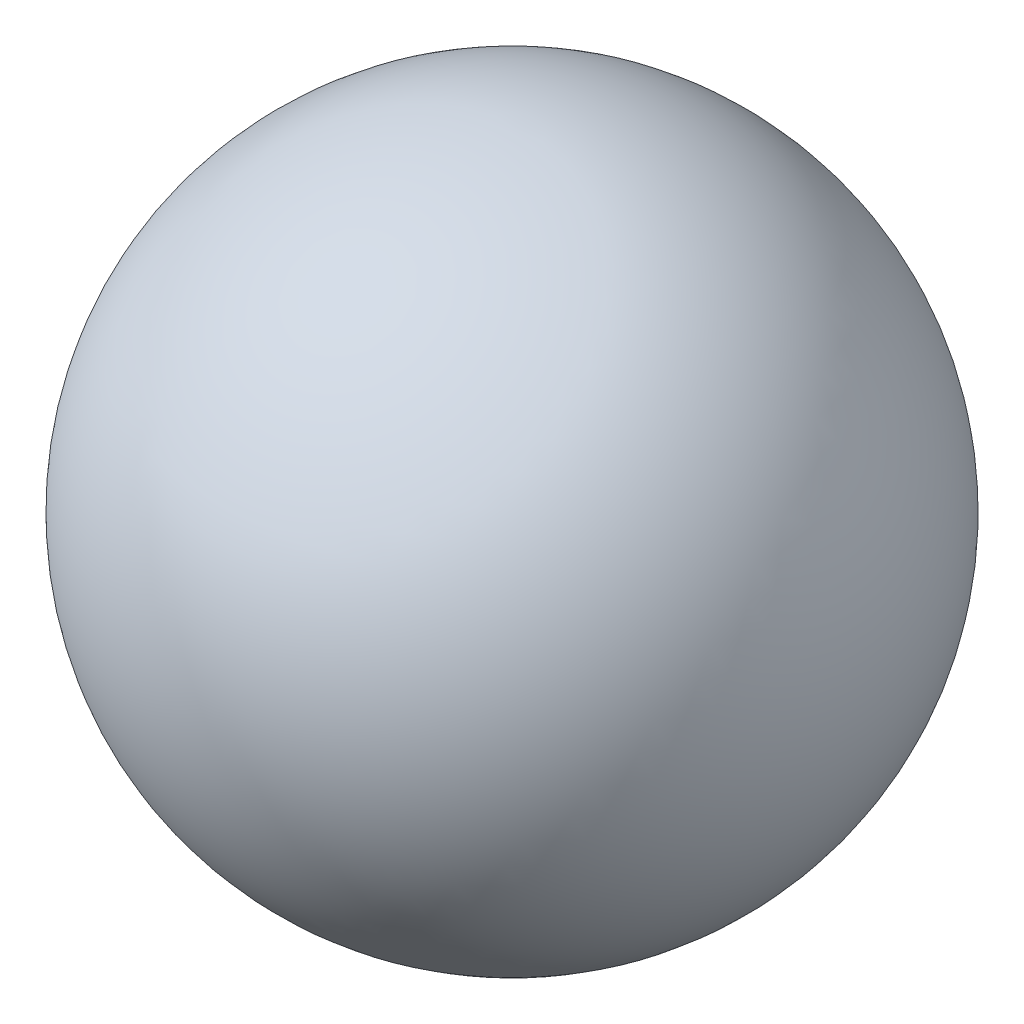
SolidWorks part; units mm, degrees
ref_plane "Front Plane" through (0, 0, 0) normal (0, 0, 1) x (1, 0, 0)
ref_plane "Top Plane" through (0, 0, 0) normal (0, 1, 0) x (1, 0, 0)
ref_plane "Right Plane" through (0, 0, 0) normal (1, 0, 0) x (0, 0, -1)
sketch "Sketch1" plane through (0, 0, 0) normal (0, 0, 1) x (1, 0, 0)
  line L0 (0, 10) -> (0, -10)
  arc A0 (0, -10) -> (0, 10) centre (0, 0) ccw
  dimension "D1" = 20
revolve "Revolve1" add sketch "Sketch1" angle 360 about L0
sketch "Sketch2" plane through (0, 0, 0) normal (0, 0, 1) x (1, 0, 0)
  line L1 (-6.9037, -11) -> (6.9037, -11)
  line L2 (-6.9037, -11) -> (-6.9037, -9)
  line L3 (-6.9037, -9) -> (6.9037, -9)
  line L4 (6.9037, -11) -> (6.9037, -9)
  line L5 (-6.9037, -11) -> (6.9037, -9) construction
  line L6 (-6.9037, -9) -> (6.9037, -11) construction
  circle A0 centre (0, 0) radius 10 construction
  point P0 (0, -10)
  dimension "D1" = 1
extrude "Cut-Extrude1" cut sketch "Sketch2" against normal through all and the other way through all
sketch "Sketch3" plane through (0, -9, 0) normal (0, -1, 0) x (1, 0, 0)
  point P0 (0, 0)
hole_wizard "M4x0.7 Tapped Hole1" positions "Sketch3" profile "Sketch4" tap size "M4x0.7" standard "ANSI Metric"
cosmetic thread "Hole Thread1" parameters "D1"=8, "D2"=4
sketch "Sketch4" plane through (0, -9, 0) normal (1, 0, 0) x (0, 0, -1)
  line L0 (0, 0) -> (0, 10.1)
  line L1 (0, 10.1) -> (1.65, 9.1086)
  line L2 (1.65, 9.1086) -> (1.65, 0)
  line L5 (1.65, 0) -> (0, 0)
  line L10 (0, 10.1) -> (-1.65, 9.1086) construction
  line L11 (0, -6.35) -> (0, 107.95) construction
  dimension "Tap Drill Dia." = 3.3
  dimension "Tap Drill Depth" = 10.1
  dimension "Drill Angle" = 118
thread "Thread1" pitch 0.7 method extrude profile "Thread Profile1" start angle 0, offset 0, length 10, pitch 0.7, diameter 3.3
ref_plane "Plane4" through (1.65, -9, 0) normal (0, 0, 1) x (1, 0, 0)
sketch "Thread Profile1" plane through (1.65, -9, 0) normal (0, 0, 1) x (1, 0, 0)
  line L0 (0, 0) -> (0, 0.7) construction
  line L11 (0, 0) -> (0, 0.6125)
  line L12 (0, 0.6125) -> (-0.3789, 0.3937)
  line L13 (-0.3789, 0.3937) -> (-0.3789, 0.2187)
  line L15 (-0.3789, 0.2187) -> (0, 0)
  line L17 (-0.3789, 0.3062) -> (0, 0.3062) construction
  point P2 (0, 0)
  dimension "Pitch" = 0.7
  dimension "Profile_Angle" = 60
  dimension "Profile_Land" = 0.175
  dimension "Profile_Height" = 0.3789
sketch "Sketch9" plane through (0, -9, 0) normal (0, -1, 0) x (1, 0, 0)
  circle A0 centre (0, 0) radius 4.3589
extrude "Cut-Extrude2" cut sketch "Sketch9" against normal blind 1 body kept at (4.3589, -9, 0)
